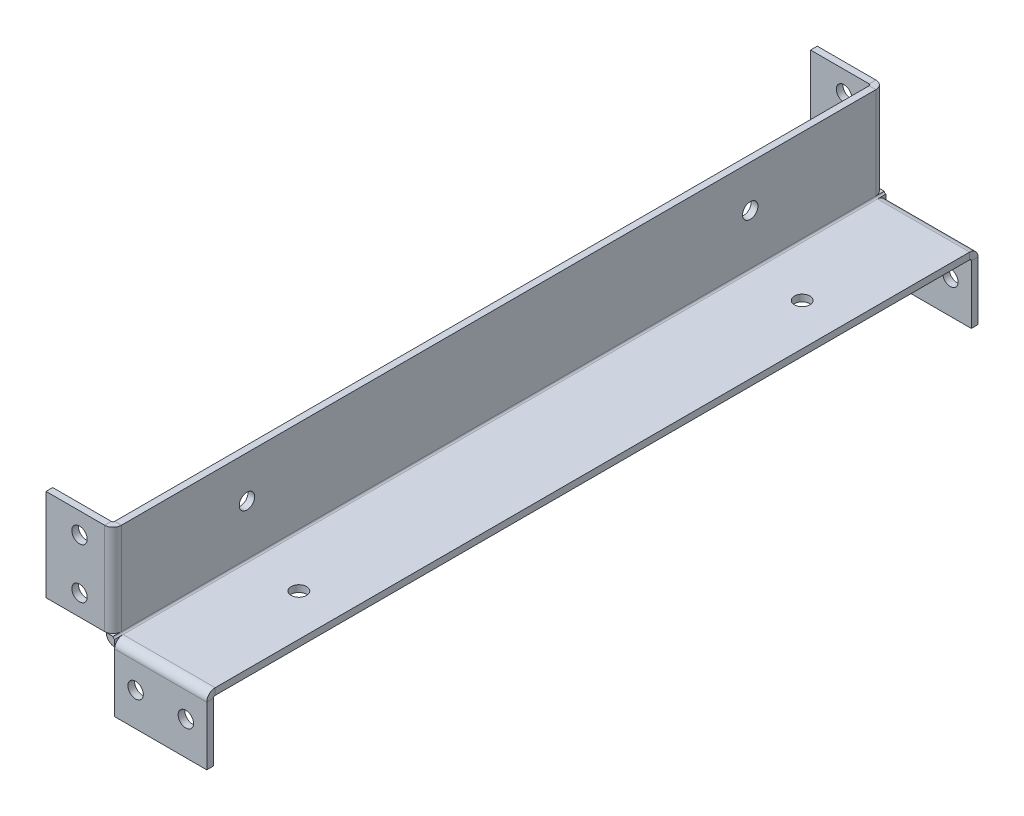
SolidWorks part; units mm, degrees
note: The reader was unsure of these and kept them because the rebuilt part matched: flange length of "Edge-Flange1", "Edge-Flange2".
ref_plane "Front Plane" through (0, 0, 0) normal (0, 0, 1) x (1, 0, 0)
ref_plane "Top Plane" through (0, 0, 0) normal (0, 1, 0) x (1, 0, 0)
ref_plane "Right Plane" through (0, 0, 0) normal (1, 0, 0) x (0, 0, -1)
sketch "Sketch1" plane through (0, 0, 0) normal (0, 1, 0) x (1, 0, 0)
  line L1 (30, 230.25) -> (-30, 230.25)
  line L2 (30, 230.25) -> (30, -230.25)
  line L3 (30, -230.25) -> (-30, -230.25)
  line L4 (-30, 230.25) -> (-30, -230.25)
  line L5 (30, 230.25) -> (-30, -230.25) construction
  line L6 (30, -230.25) -> (-30, 230.25) construction
  point P0 (0, 0)
  dimension "D1" = 60
  dimension "D2" = 460.5
sheet metal parameters "Sheet-Metal1" thickness 4 parameters "D1"=1
base flange "Base-Flange1" sketch "Sketch1" thickness 4 reverse thickness direction yes parameters "D1"=1
edge flange "Edge-Flange1" sketch "Sketch5" flange angle 90 flange length 60 flange position material inside bend radius 1 thickness 4 parameters "D6"=10
sketch "Sketch5" plane through (-30, 4, 0) normal (-1, 0, 0) x (0, 0, 1)
  line L2 (-230.25, 0) -> (-230.25, 56)
  line L3 (-230.25, 56) -> (230.25, 56)
  line L4 (230.25, 56) -> (230.25, 0)
  line L5 (-230.25, 0) -> (230.25, 0) construction
  line L6 (-230.25, 0) -> (230.25, 0)
bend "EdgeBend1" bend radius 1 bend angle 90 parameters "D5"=1
edge flange "Edge-Flange2" sketch "Sketch14" flange profiles "Sketch14", "Sketch15", "Sketch16", "Sketch17" flange angle 90 flange length 40 flange position material inside bend radius 1 thickness 4 relief none parameters "D6"=10, "D8"=0.5
sketch "Sketch14" plane through (-30, 0, 230.25) normal (0, 0, -1) x (0, -1, 0)
  line L1 (-5, 0) -> (-60, 0) construction
  line L2 (-60, 0) -> (-60, 36)
  line L3 (-60, 36) -> (-5, 36)
  line L4 (-5, 36) -> (-5, 0)
  line L5 (-5, 0) -> (-60, 0)
sketch "Sketch15" plane through (0, 0, 230.25) normal (0, 0, -1) x (1, 0, 0)
  line L0 (30, 0) -> (-25, 0) construction
  line L1 (30, 0) -> (-25, 0)
  line L2 (30, 0) -> (30, 36)
  line L3 (30, 36) -> (-25, 36)
  line L4 (-25, 36) -> (-25, 0)
sketch "Sketch16" plane through (-30, 0, -230.25) normal (0, 0, 1) x (0, 1, 0)
  line L0 (60, 0) -> (5, 0) construction
  line L1 (60, 0) -> (5, 0)
  line L2 (60, 0) -> (60, 36)
  line L3 (60, 36) -> (5, 36)
  line L4 (5, 36) -> (5, 0)
sketch "Sketch17" plane through (0, 0, -230.25) normal (0, 0, 1) x (-1, 0, 0)
  line L0 (25, 0) -> (-30, 0) construction
  line L1 (25, 0) -> (-30, 0)
  line L2 (25, 0) -> (25, 36)
  line L3 (25, 36) -> (-30, 36)
  line L4 (-30, 36) -> (-30, 0)
bend "EdgeBend2" bend radius 1 bend angle 90 parameters "D5"=2
bend "EdgeBend3" bend radius 1 bend angle 90 parameters "D5"=3
bend "EdgeBend4" bend radius 1 bend angle 90 parameters "D5"=4
bend "EdgeBend5" bend radius 1 bend angle 90 parameters "D5"=5
sketch "Sketch18" plane through (0, 0, 230.25) normal (0, 0, 1) x (1, 0, 0)
  line L0 (-25, 4) -> (30, 4) construction
  line L1 (-26, 60) -> (-26, 5) construction
  line L2 (-66, 60) -> (-31, 60) construction
  line L3 (30, -1) -> (30, -36) construction
  circle A0 centre (-46, 47.5) radius 4.6
  circle A1 centre (-46, 17.5) radius 4.6
  circle A2 centre (-12.5, -16) radius 4.6
  circle A3 centre (17.5, -16) radius 4.6
  dimension "D7" = 9.2
  dimension "D1" = 30
  dimension "D2" = 30
  dimension "D3" = 20
  dimension "D4" = 20
  dimension "D5" = 12.5
  dimension "D6" = 12.5
extrude "Extrude1" cut sketch "Sketch18" against normal through all normal cut yes
sketch "Sketch19" plane through (-26, 0, 0) normal (1, 0, 0) x (0, 0, -1)
  line L0 (-225.25, 60) -> (225.25, 60) construction
  line L1 (-230.25, 5) -> (-230.25, 60) construction
  line L2 (230.25, 5) -> (230.25, 60) construction
  circle A0 centre (-150.25, 35) radius 4.6
  circle A1 centre (150.25, 35) radius 4.6
  dimension "D4" = 9.2
  dimension "D1" = 25
  dimension "D2" = 80
  dimension "D3" = 80
extrude "Extrude2" cut sketch "Sketch19" against normal blind 4 normal cut yes
sketch "Sketch20" plane through (0, 4, 0) normal (0, 1, 0) x (1, 0, 0)
  line L0 (30, -225.25) -> (30, 225.25) construction
  line L1 (-25, -230.25) -> (30, -230.25) construction
  line L2 (30, 230.25) -> (-25, 230.25) construction
  circle A0 centre (5, 150.25) radius 4.6
  circle A1 centre (5, -150.25) radius 4.6
  dimension "D2" = 9.2
  dimension "D1" = 25
  dimension "D3" = 80
  dimension "D4" = 80
extrude "Extrude3" cut sketch "Sketch20" against normal blind 4 normal cut yes
flat pattern "Flat-Pattern1" [suppressed]
sketch "Bend-Lines1" plane through (0, 4, 0) normal (0, 1, 0) x (-1, 0, 0)
  line L0 (25, -199.4012) -> (-30, -199.4012) construction
  line L1 (82.8023, -199.4012) -> (27.8023, -199.4012) construction
  line L2 (-30, 199.4012) -> (25, 199.4012) construction
  line L3 (27.8023, 199.4012) -> (82.8023, 199.4012) construction
  line L4 (26.4012, -203) -> (26.4012, 203) construction
  line L5 (25, -199.4012) -> (-30, -199.4012) construction
  line L6 (82.8023, -199.4012) -> (27.8023, -199.4012) construction
  line L7 (-30, 199.4012) -> (25, 199.4012) construction
  line L8 (27.8023, 199.4012) -> (82.8023, 199.4012) construction
  line L9 (26.4012, -203) -> (26.4012, 203) construction
sketch3d "Bounding-Box1" [suppressed]
  line L0 (52.8023, 32.8023, 0) -> (52.8023, -438.8023, 0) construction
  line L1 (-60, 32.8023, 0) -> (-60, -438.8023, 0) construction
  line L2 (52.8023, 32.8023, 0) -> (-60, 32.8023, 0) construction
  line L3 (52.8023, -438.8023, 0) -> (-60, -438.8023, 0) construction
bend of the flat pattern "Flatten-<EdgeBend1>1"
bend of the flat pattern "Flatten-<EdgeBend2>1"
bend of the flat pattern "Flatten-<EdgeBend3>1"
bend of the flat pattern "Flatten-<EdgeBend4>1"
bend of the flat pattern "Flatten-<EdgeBend5>1"
